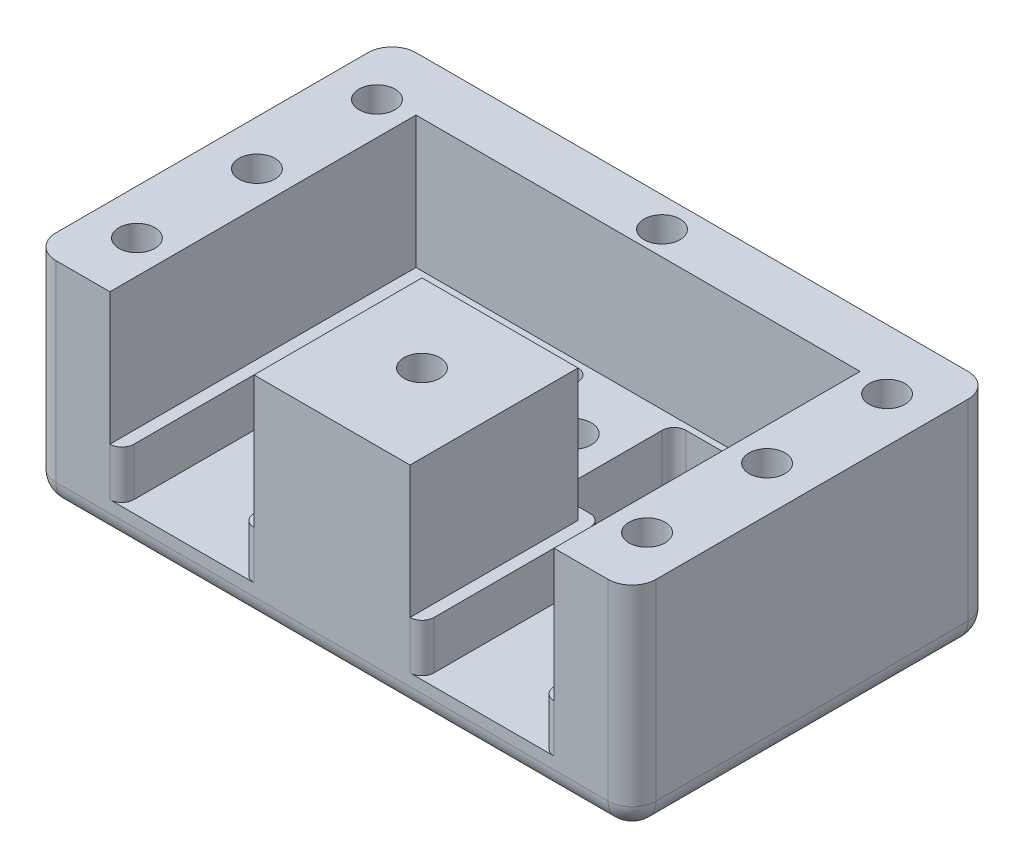
SolidWorks part; units mm, degrees
material "ABS"
ref_plane "Спереди" through (0, 0, 0) normal (0, 0, 1) x (1, 0, 0)
ref_plane "Сверху" through (0, 0, 0) normal (0, 1, 0) x (1, 0, 0)
ref_plane "Справа" through (0, 0, 0) normal (1, 0, 0) x (0, 0, -1)
sketch "Эскиз1" plane through (0, 0, 0) normal (0, 1, 0) x (1, 0, 0)
  line L1 (25, -15) -> (-25, -15)
  line L2 (25, -15) -> (25, 15)
  line L3 (25, 15) -> (-25, 15)
  line L4 (-25, -15) -> (-25, 15)
  line L5 (25, -15) -> (-25, 15) construction
  line L6 (25, 15) -> (-25, -15) construction
  point P0 (0, 0)
  dimension "D1" = 30
  dimension "D2" = 50
extrude "Бобышка-Вытянуть1" add sketch "Эскиз1" along normal blind 7
sketch "Эскиз2" plane through (0, 7, 0) normal (0, 1, 0) x (1, 0, 0)
  line L0 (-25, -15) -> (25, -15) construction
  line L1 (-17.5, 10) -> (-7.5, 10)
  line L2 (-17.5, 10) -> (-17.5, -15)
  line L3 (-17.5, -15) -> (-7.5, -15)
  line L4 (-7.5, 10) -> (-7.5, -15)
  line L6 (7.5, 10) -> (17.5, 10)
  line L7 (7.5, 10) -> (7.5, -15)
  line L8 (7.5, -15) -> (17.5, -15)
  line L9 (17.5, 10) -> (17.5, -15)
extrude "Вырез-Вытянуть1" cut sketch "Эскиз2" against normal blind 4
sketch "Эскиз4" plane through (0, 7, 0) normal (0, 1, 0) x (1, 0, 0)
  circle A0 centre (0, 5) radius 1.6
  dimension "D1" = 3.2
extrude "Вырез-Вытянуть3" cut sketch "Эскиз4" against normal through all
sketch "Эскиз5" plane through (0, 0, 0) normal (0, -1, 0) x (1, 0, 0)
  circle A0 centre (0, -5) radius 3
  dimension "D1" = 6
extrude "Вырез-Вытянуть4" cut sketch "Эскиз5" against normal blind 3
sketch "Эскиз6" plane through (0, 7, 0) normal (0, 1, 0) x (1, 0, 0)
  line L0 (0, 15) -> (0, 10) construction
  line L1 (25, 15) -> (-25, 15) construction
  line L2 (-25, 0) -> (-17.5, 0) construction
  line L3 (-25, 15) -> (-25, -15) construction
  line L4 (-17.5, 10) -> (-17.5, -15) construction
  line L5 (25, 0) -> (17.5, 0) construction
  line L6 (25, -15) -> (25, 15) construction
  line L7 (17.5, -15) -> (17.5, 10) construction
  line L8 (0, -15) -> (0, 0) construction
  line L9 (-7.5, -15) -> (7.5, -15) construction
  circle A0 centre (-21.25, 0) radius 1.5
  circle A1 centre (0, 12.5) radius 1.5
  circle A2 centre (21.25, 0) radius 1.5
  circle A3 centre (0, -7.5) radius 1.5
extrude "Вырез-Вытянуть5" cut sketch "Эскиз6" against normal through all
sketch "Эскиз7" plane through (0, 7, 0) normal (0, 1, 0) x (1, 0, 0)
  line L0 (25, 15) -> (-25, 15) construction
  line L1 (-25, 15) -> (25, 15)
  line L2 (-25, 15) -> (-25, -15)
  line L4 (25, 15) -> (25, -15)
  line L5 (25, -15) -> (25, 15) construction
  line L25 (-18.5, -15) -> (-18.5, 10.5)
  line L27 (18.5, 10.5) -> (18.5, -15)
  line L28 (-25, -15) -> (-18.5, -15)
  line L29 (18.5, -15) -> (25, -15)
  line L30 (-6.5, -15) -> (6.5, -15)
  line L33 (-18.5, 10.5) -> (18.5, 10.5)
  line L36 (-6.5, -15) -> (-6.5, -1)
  line L37 (-6.5, -1) -> (6.5, -1)
  line L38 (6.5, -1) -> (6.5, -15)
extrude "Бобышка-Вытянуть6" add sketch "Эскиз7" along normal blind 11
sketch "Эскиз8" plane through (0, 7, 0) normal (0, -1, 0) x (1, 0, 0)
  circle A0 centre (21.25, 0) radius 1.5
  circle A1 centre (0, 7.5) radius 1.5
  circle A2 centre (-21.25, 0) radius 1.5
  circle A3 centre (0, -12.5) radius 1.5
extrude "Вырез-Вытянуть6" cut sketch "Эскиз8" against normal through all
sketch "Эскиз9" plane through (0, 18, 0) normal (0, 1, 0) x (1, 0, 0)
  circle A0 centre (-21.25, 10) radius 1.5
  circle A1 centre (21.25, 10) radius 1.5
  circle A2 centre (21.25, -10) radius 1.5
  circle A3 centre (-21.25, -10) radius 1.5
extrude "Вырез-Вытянуть7" cut sketch "Эскиз9" against normal through all
fillet "Скругление1" radius 2 8 edges at (0, 0, 15) (-25, 9, 15) (-25, 0, 0) (-25, 9, -15) (0, 0, -15) (25, 9, -15) (25, 0, 0) (25, 9, 15)
sketch "Эскиз10" plane through (0, 7, 0) normal (0, 1, 0) x (1, 0, 0)
  line L0 (-7.5, -15) -> (-7.5, 10) construction
  line L1 (-7.5, 10) -> (-3.5, 10)
  line L2 (-7.5, 10) -> (-7.5, 0)
  line L3 (-7.5, 0) -> (-3.5, 0)
  line L4 (-3.5, 10) -> (-3.5, 0)
  line L5 (7.5, 10) -> (7.5, -15) construction
  line L6 (7.5, 10) -> (3.5, 10)
  line L7 (7.5, 10) -> (7.5, 0)
  line L8 (7.5, 0) -> (3.5, 0)
  line L9 (3.5, 10) -> (3.5, 0)
  line L10 (17.5, 10) -> (7.5, 10) construction
  dimension "D1" = 4
  dimension "D2" = 4
extrude "Вырез-Вытянуть8" cut sketch "Эскиз10" against normal up to surface (4 mm away) up to face at (-12.5, 3, 2.5)
fillet "Скругление2" radius 1 6 edges at (7.5, 5, 0) (3.5, 5, 0) (3.5, 5, -10) (-3.5, 5, -10) (-7.5, 5, 0) (-3.5, 5, 0)
fillet "Скругление3" radius 1 6 edges at (17.5, 5, -10) (17.5, 5, 15) (7.5, 5, 15) (-7.5, 5, 15) (-17.5, 5, 15) (-17.5, 5, -10)
